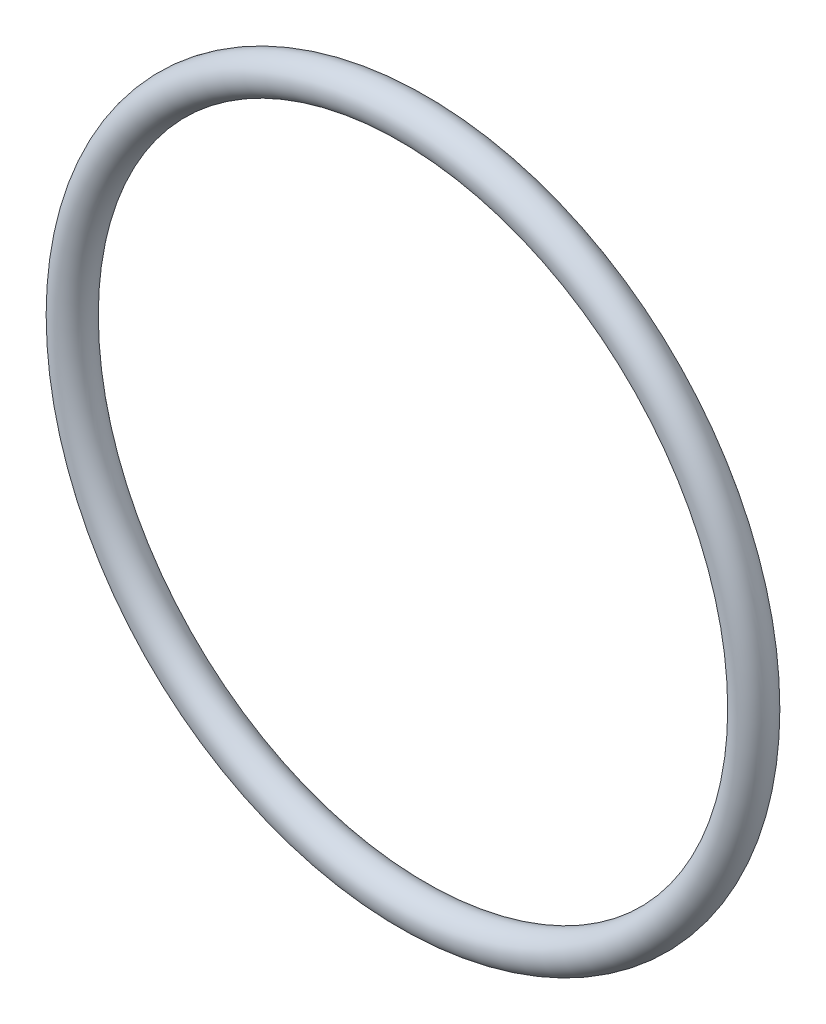
SolidWorks part; units mm, degrees
ref_plane "Front Plane" through (0, 0, 0) normal (0, 0, 1) x (1, 0, 0)
ref_plane "Top Plane" through (0, 0, 0) normal (0, 1, 0) x (1, 0, 0)
ref_plane "Right Plane" through (0, 0, 0) normal (1, 0, 0) x (0, 0, -1)
sketch "Sketch1" plane through (0, 0, 0) normal (1, 0, 0) x (0, 0, -1)
  line L0 (-18.1323, 0) -> (23.0027, 0) construction
  circle A0 centre (0, 24.1554) radius 1.3081
  point P5 (1.3081, 24.1554)
  point P6 (0, 22.8473)
  dimension "D2" = 2.6162
  dimension "D1" = 45.6946
revolve "Revolve1" add sketch "Sketch1" angle 360 about L0
ref_plane "Plane1" through (0, 0, -1.3081) normal (0, 0, 1) x (1, 0, 0)
ref_axis "Axis1" through (0, 0, 18.1323) along (0, 0, -1)
